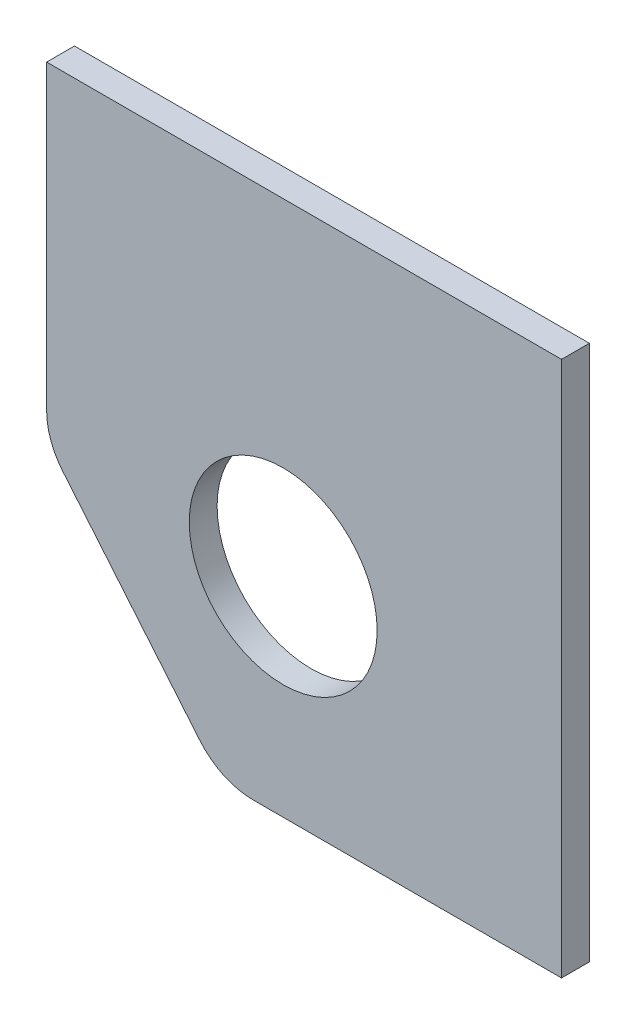
SolidWorks part; units mm, degrees
ref_plane "Plano frontal" through (0, 0, 0) normal (0, 0, 1) x (1, 0, 0)
ref_plane "Plano superior" through (0, 0, 0) normal (0, 1, 0) x (1, 0, 0)
ref_plane "Plano direito" through (0, 0, 0) normal (1, 0, 0) x (0, 0, -1)
sketch "Esboço1" plane through (0, 0, 0) normal (0, 0, 1) x (1, 0, 0)
  line L1 (-86.1657, 44.0263) -> (-12.1657, 44.0263)
  line L2 (-86.1657, 44.0263) -> (-86.1657, -32.9737)
  line L3 (-86.1657, -32.9737) -> (-12.1657, -32.9737)
  line L4 (-12.1657, 44.0263) -> (-12.1657, -32.9737)
  dimension "D1" = 77
  dimension "D2" = 74
extrude "Ressalto-extrusão1" add sketch "Esboço1" along normal blind 4
sketch "Esboço2" plane through (0, 0, 4) normal (0, 0, 1) x (1, 0, 0)
  circle A0 centre (-52.1657, -2.9737) radius 13.5
  dimension "D1" = 27
  dimension "D2" = 34
  dimension "D3" = 30
extrude "Corte-extrusão1" cut sketch "Esboço2" against normal blind 4 and the other way blind 4
sketch "Esboço4" plane through (0, 0, 4) normal (0, 0, 1) x (1, 0, 0)
  line L0 (-61.1657, -32.9737) -> (-86.1657, -2.9737)
  line L1 (-86.1657, -32.9737) -> (-12.1657, -32.9737) construction
  line L2 (-86.1657, 44.0263) -> (-86.1657, -32.9737) construction
  dimension "D1" = 30
  dimension "D2" = 25
extrude "Corte-extrusão2" cut sketch "Esboço4" against normal through all and the other way through all
fillet "Filete2" radius 10 1 edges at (-86.1657, -2.9737, 2) type face fillet first side face at (-86.1657, 20.5263, 2) second side face at (-73.6657, -17.9737, 2)
fillet "Filete3" radius 10 1 edges at (-61.1657, -32.9737, 2) type face fillet first side face at (-72.5068, -19.3644, 2) second side face at (-36.6657, -32.9737, 2)
